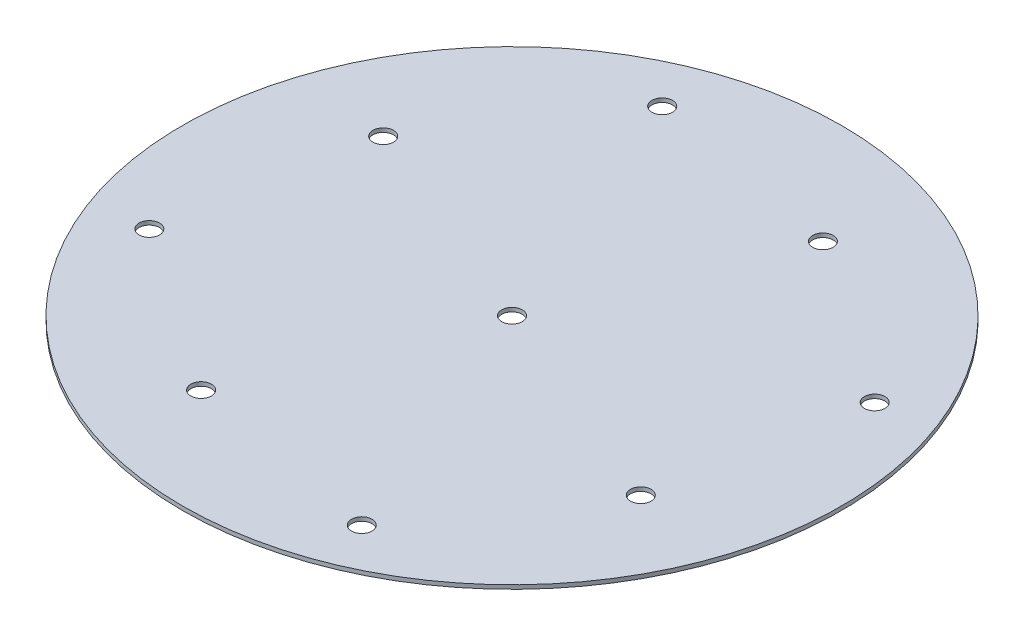
SolidWorks part; units mm, degrees
ref_plane "Front Plane" through (0, 0, 0) normal (0, 0, 1) x (1, 0, 0)
ref_plane "Top Plane" through (0, 0, 0) normal (0, 1, 0) x (1, 0, 0)
ref_plane "Right Plane" through (0, 0, 0) normal (1, 0, 0) x (0, 0, -1)
sketch "Sketch2" plane through (0, 0, 0) normal (1, 0, 0) x (0, 0, -1)
  line L0 (0, 0) -> (-83.0999, 0)
  line L1 (-83.0999, 0) -> (-83.0999, 1)
  line L2 (-83.0999, 1) -> (0, 1)
  line L5 (0, 1) -> (0, 0)
  dimension "D1" = 83.0999
  dimension "D2" = 1
ref_axis "Axis1" through (0, -0.05, 0) along (0, 1, 0)
revolve "Revolve1" add sketch "Sketch2" angle 360 about axis through (0, -0.05, 0) along (0, 1, 0)
hole_wizard "#6 (0.204) Diameter Hole1" positions "Sketch6" profile "Sketch7" hole size "#6" standard "ANSI Inch" end condition through all
sketch "Sketch6" plane through (0, 1, 0) normal (0, 1, 0) x (1, 0, 0)
  line L0 (0, 0) -> (-53.438, 129.0108) construction
  line L2 (0, 0) -> (0, 109.0908) construction
  line L3 (0, 0) -> (-76.7743, 31.801) construction
  circle A0 centre (0, 0) radius 83.0999 construction
  point P0 (-26.7878, 64.6716)
  point P11 (264.7437, 73.7878)
  point P20 (-55.4328, 22.961)
  dimension "D1" = 22.5
  dimension "D2" = 70
  dimension "D3" = 60
  dimension "D4" = 45
sketch "Sketch7" plane through (-26.7878, 1, -64.6716) normal (1, 0, 0) x (0, 0, 1)
  line L0 (0, 0) -> (0, 1)
  line L1 (0, 1) -> (2.5908, 1)
  line L2 (2.5908, 1) -> (2.5908, 0)
  line L5 (2.5908, 0) -> (0, 0)
  line L11 (0, -6.35) -> (0, 107.95) construction
  dimension "Thru Hole Dia." = 5.1816
  dimension "Thru Hole Depth" = 1
pattern_circular "CirPattern3" count 4 over 360 about axis through (0, -0.05, 0) along (0, 1, 0) of "#6 (0.204) Diameter Hole1"
hole_wizard "#6 (0.204) Diameter Hole2" positions "Sketch8" profile "Sketch9" hole size "#6" standard "ANSI Inch" end condition through all
sketch "Sketch8" plane through (0, 1, 0) normal (0, 1, 0) x (1, 0, 0)
  line L0 (0, 0) -> (106.3094, -1.7118) construction
  point P7 (0, 0)
sketch "Sketch9" plane through (0, 1, 0) normal (1, 0, 0) x (0, 0, 1)
  line L0 (0, 0) -> (0, 1)
  line L1 (0, 1) -> (2.5908, 1)
  line L2 (2.5908, 1) -> (2.5908, 0)
  line L5 (2.5908, 0) -> (0, 0)
  line L11 (0, -6.35) -> (0, 107.95) construction
  dimension "Thru Hole Dia." = 5.1816
  dimension "Thru Hole Depth" = 1
equation "\"TubeDiameter\" = 6.5433in"
equation "\"D1@Sketch2\"=\"TubeDiameter\"/2"
